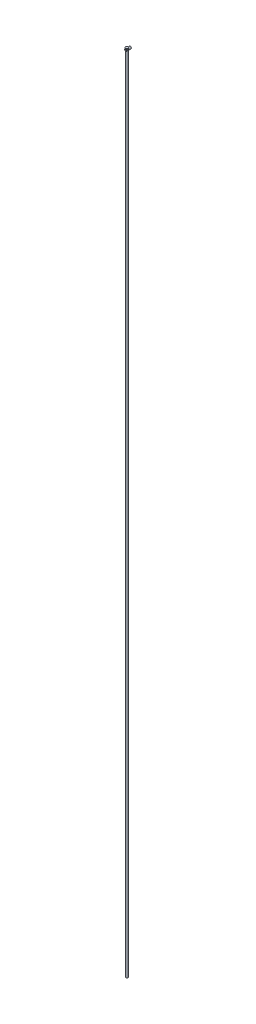
SolidWorks part; units mm, degrees
ref_plane "Alzado" through (0, 0, 0) normal (0, 0, 1) x (1, 0, 0)
ref_plane "Planta" through (0, 0, 0) normal (0, 1, 0) x (1, 0, 0)
ref_plane "Vista lateral" through (0, 0, 0) normal (1, 0, 0) x (0, 0, -1)
sketch "Croquis1" plane through (0, 0, 0) normal (0, 0, 1) x (1, 0, 0)
  circle A0 centre (0, 0) radius 12.7
  circle A1 centre (0, 0) radius 10
extrude "Saliente-Extruir1" add sketch "Croquis1" along normal blind 50
ref_plane "Plano1" through (0, -12.7, 0) normal (0, 1, 0) x (1, 0, 0)
sketch "Croquis2" plane through (0, -12.7, 0) normal (0, 1, 0) x (1, 0, 0)
  circle A0 centre (0, -37.25) radius 12.7
extrude "Saliente-Extruir2" add sketch "Croquis2" against normal blind 8969.1 and the other way blind 25.4
sketch "Croquis3" plane through (0, -12.7, 0) normal (0, 1, 0) x (1, 0, 0)
  circle A0 centre (0, -37.25) radius 10
extrude "Cortar-Extruir1" cut sketch "Croquis3" along normal through all both and the other way through all
sketch "Croquis4" plane through (0, 0, 0) normal (0, 0, 1) x (1, 0, 0)
  circle A0 centre (0, 0) radius 10
extrude "Cortar-Extruir2" cut sketch "Croquis4" along normal blind 42
ref_plane "Plano2" through (0, 12.7, 0) normal (0, 1, 0) x (1, 0, 0)
sketch "Croquis5" plane through (0, 12.7, 0) normal (0, 1, 0) x (1, 0, 0)
  circle A0 centre (0, -37.25) radius 14.5
extrude "Saliente-Extruir4" add sketch "Croquis5" along normal blind 5 separate body
